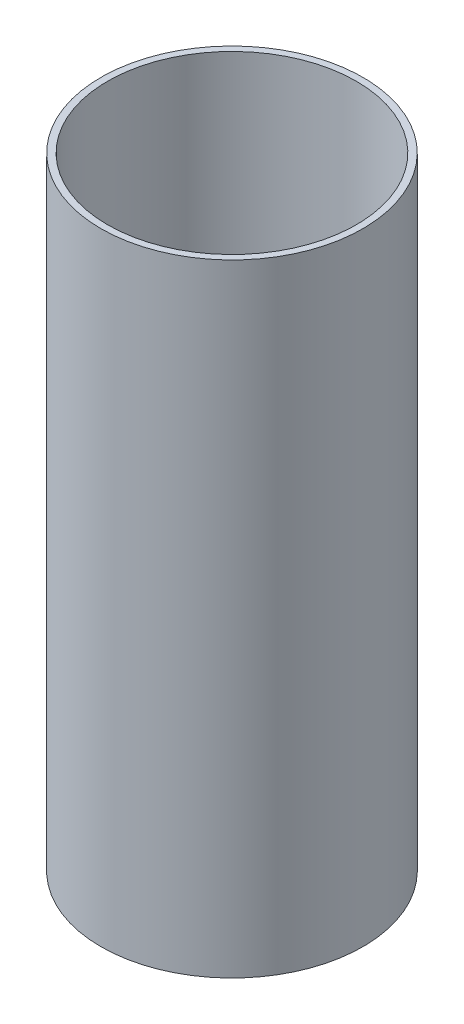
SolidWorks part; units mm, degrees
material "PVC Rigid"
ref_plane "Front Plane" through (0, 0, 0) normal (0, 0, 1) x (1, 0, 0)
ref_plane "Top Plane" through (0, 0, 0) normal (0, 1, 0) x (1, 0, 0)
ref_plane "Right Plane" through (0, 0, 0) normal (1, 0, 0) x (0, 0, -1)
sketch "Sketch1" plane through (0, 0, 0) normal (0, 1, 0) x (1, 0, 0)
  circle A0 centre (0, 0) radius 93.6625
  circle A1 centre (0, 0) radius 88.9
  dimension "D1" = 187.325
  dimension "D2" = 177.8
extrude "Boss-Extrude1" add sketch "Sketch1" along normal mid plane 444.5
ref_plane "Plane1" through (-93.6625, 0, 0) normal (-1, 0, 0) x (0, 0, 1)
sketch "Sketch3" plane through (-93.6625, 0, 0) normal (-1, 0, 0) x (0, 0, 1)
  line L0 (0, -103.0288) -> (0, 103.0288) construction
  line L1 (-88.9, -222.25) -> (88.9, -222.25) construction
  circle A0 centre (0, -215.9) radius 1.4351
  dimension "D1" = 2.8702
  dimension "D2" = 6.35
extrude "Cut-Extrude1" [suppressed] cut sketch "Sketch3" against normal blind 21.59
pattern_circular "CirPattern1" [suppressed] count 12 over 360 reverse direction yes of bodies 102
sketch "Sketch4" plane through (-93.6625, 0, 0) normal (-1, 0, 0) x (0, 0, 1)
  line L0 (0, -103.0288) -> (0, 103.0288) construction
  line L1 (93.6625, 222.25) -> (-93.6625, 222.25) construction
  circle A0 centre (0, 215.9) radius 1.4351
  dimension "D1" = 2.8702
  dimension "D2" = 6.35
extrude "Cut-Extrude2" [suppressed] cut sketch "Sketch4" against normal blind 34.798
pattern_circular "CirPattern2" [suppressed] count 3 over 360 reverse direction yes of bodies 104
sketch "Sketch9" [suppressed] plane through (-93.6625, 0, 0) normal (-1, 0, 0) x (0, 0, 1)
  line L0 (0, -103.0288) -> (0, 103.0288) construction
  circle A0 centre (0, 136.398) radius 1.4351
  circle A1 centre (0, 215.9) radius 1.4351 construction
  dimension "D1" = 79.502
  dimension "D2" = 2.8702
extrude "Cut-Extrude4" [suppressed] cut sketch "Sketch9" against normal blind 15.24
pattern_circular "CirPattern4" [suppressed] count 12 over 360 of bodies 108
sketch "Sketch7" [suppressed] plane through (-93.6625, 0, 0) normal (-1, 0, 0) x (0, 0, 1)
  line L0 (0, -103.0288) -> (0, 103.0288) construction
  circle A0 centre (0, 19.05) radius 1.4351
  circle A1 centre (0, -98.552) radius 1.4351
  circle A4 centre (0, 136.398) radius 1.4351 construction
  circle A5 centre (0, -215.9) radius 1.4351 construction
  dimension "D1" = 117.348
  dimension "D2" = 117.348
  dimension "D3" = 2.8702
  dimension "D4" = 2.8702
extrude "Cut-Extrude3" [suppressed] cut sketch "Sketch7" against normal blind 15.24
pattern_circular "CirPattern3" [suppressed] count 3 over 360 reverse direction yes of bodies 106
